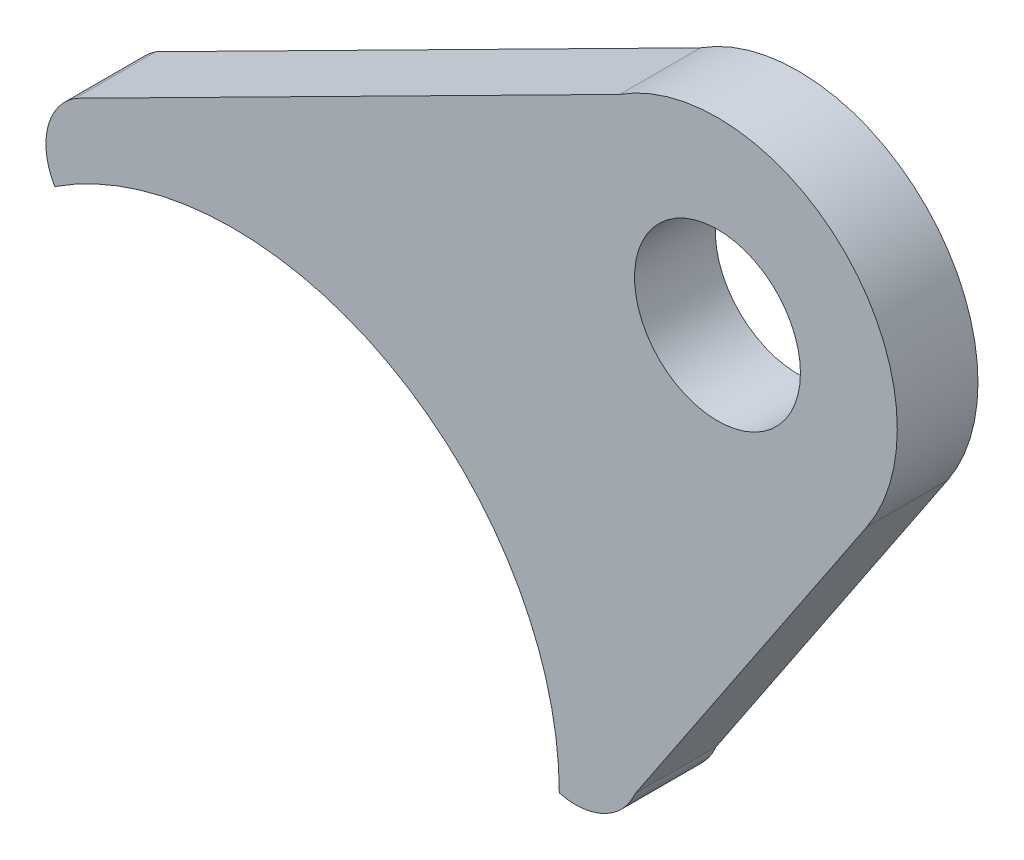
SolidWorks part; units mm, degrees
ref_plane "Front Plane" through (0, 0, 0) normal (0, 0, 1) x (1, 0, 0)
ref_plane "Top Plane" through (0, 0, 0) normal (0, 1, 0) x (1, 0, 0)
ref_plane "Right Plane" through (0, 0, 0) normal (1, 0, 0) x (0, 0, -1)
sketch "Sketch1" plane through (0, 0, 0) normal (0, 0, 1) x (1, 0, 0)
  line L4 (-6.213, 14.1464) -> (15.2029, 24.9863)
  line L5 (15.8115, 1.4683) -> (24.932, 15.1204)
  arc A0 (12.827, 0) -> (-7.0243, 10.7327) centre (0, 0) ccw
  circle A1 centre (19.05, 19.05) radius 3.2639
  arc A4 (24.932, 15.1204) -> (15.2029, 24.9863) centre (19.05, 19.05) ccw
  arc A5 (-7.0243, 10.7327) -> (-6.213, 14.1464) centre (-4.8316, 12.0149) cw
  arc A6 (12.827, 0) -> (15.8115, 1.4683) centre (13.4718, 2.4568) ccw
  point P5 (15.7236, 0.3037)
  point P10 (13.4718, 2.4568)
  point P15 (14.4189, 2.7433)
  dimension "D1" = 25.654
  dimension "D2" = 6.5278
  dimension "D5" = 14.1478
  dimension "D6" = 2.54
  dimension "D3" = 19.05
  dimension "D4" = 19.05
extrude "Boss-Extrude1" add sketch "Sketch1" along normal blind 3.175
